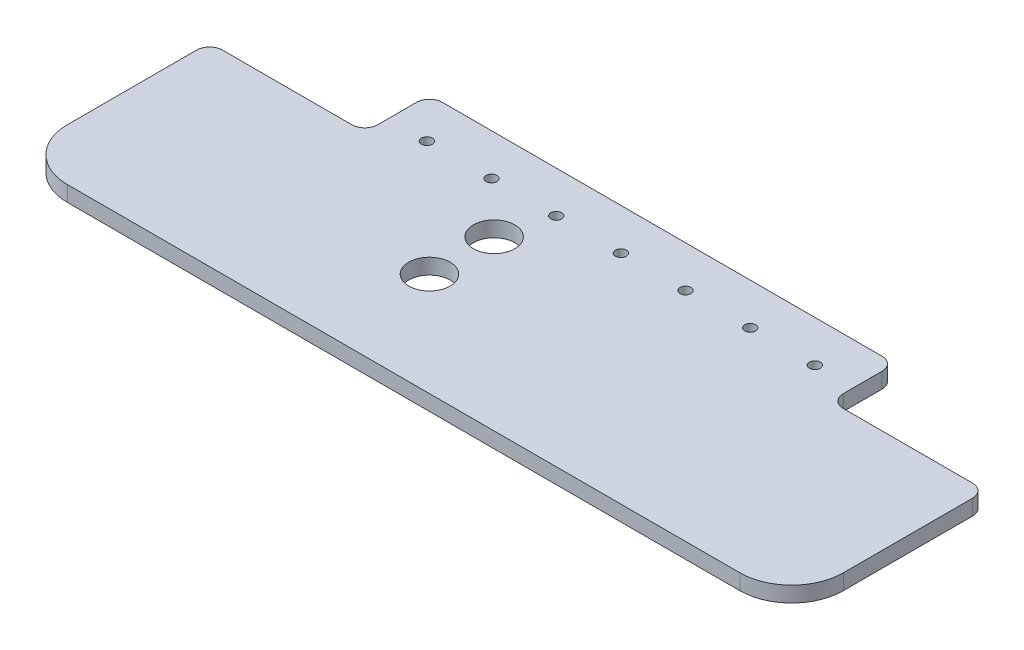
SolidWorks part; units mm, degrees
ref_plane "前视基准面" through (0, 0, 0) normal (0, 0, 1) x (1, 0, 0)
ref_plane "上视基准面" through (0, 0, 0) normal (0, 1, 0) x (1, 0, 0)
ref_plane "右视基准面" through (0, 0, 0) normal (1, 0, 0) x (0, 0, -1)
other "Configuration Table"
sketch "草图1" plane through (0, 0, 0) normal (0, 1, 0) x (1, 0, 0)
  line L0 (90, 50) -> (90, 25)
  line L1 (-150, -50) -> (150, -50)
  line L2 (-150, -50) -> (-150, 25)
  line L3 (-90, 50) -> (90, 50)
  line L4 (150, -50) -> (150, 25)
  line L5 (-150, -50) -> (150, 50) construction
  line L6 (-150, 50) -> (150, -50) construction
  line L7 (90, 25) -> (150, 25)
  line L8 (0, 0) -> (0, 50) construction
  line L9 (-90, 25) -> (-150, 25)
  line L10 (-90, 50) -> (-90, 25)
  circle A0 centre (0, 34) radius 2.1
  circle A1 centre (25, 34) radius 2.1
  circle A2 centre (50, 34) radius 2.1
  circle A3 centre (75, 34) radius 2.1
  circle A4 centre (-25, 34) radius 2.1
  circle A5 centre (-50, 34) radius 2.1
  circle A6 centre (-75, 34) radius 2.1
  point P0 (0, 0)
  dimension "D5" = 4.2
  dimension "D1" = 300
  dimension "D2" = 100
  dimension "D3" = 180
  dimension "D4" = 25
  dimension "D6" = 16
  dimension "D7" = 4
  dimension "D8" = 4
extrude "凸台-拉伸1" add sketch "草图1" along normal blind 6
fillet "圆角1" radius 5 4 edges at (-90, 3, -25) (-90, 3, -50) (90, 3, -25) (90, 3, -50)
fillet "圆角2" radius 20 2 edges at (150, 3, 50) (-150, 3, 50)
chamfer "倒角1" distance 3 angle 45 7 edges at (75, 0, -31.9) (50, 0, -31.9) (25, 0, -31.9) (0, 0, -31.9) (-25, 0, -31.9) (-50, 0, -31.9) (-75, 0, -31.9)
fillet "圆角3" radius 5 2 edges at (-150, 3, -25) (150, 3, -25)
sketch "草图2" plane through (0, 0, 0) normal (0, -1, 0) x (1, 0, 0)
  line L0 (-150, -20) -> (-150, 30) construction
  line L2 (-130, 50) -> (130, 50) construction
  circle A0 centre (-30, 10) radius 8
  circle A1 centre (-30, -15) radius 8
  point P6 (-130.747, 14.7627)
  dimension "D1" = 16
  dimension "D2" = 16
  dimension "D3" = 25
  dimension "D4" = 120
  dimension "D5" = 40
extrude "切除-拉伸1" cut sketch "草图2" against normal blind 10
